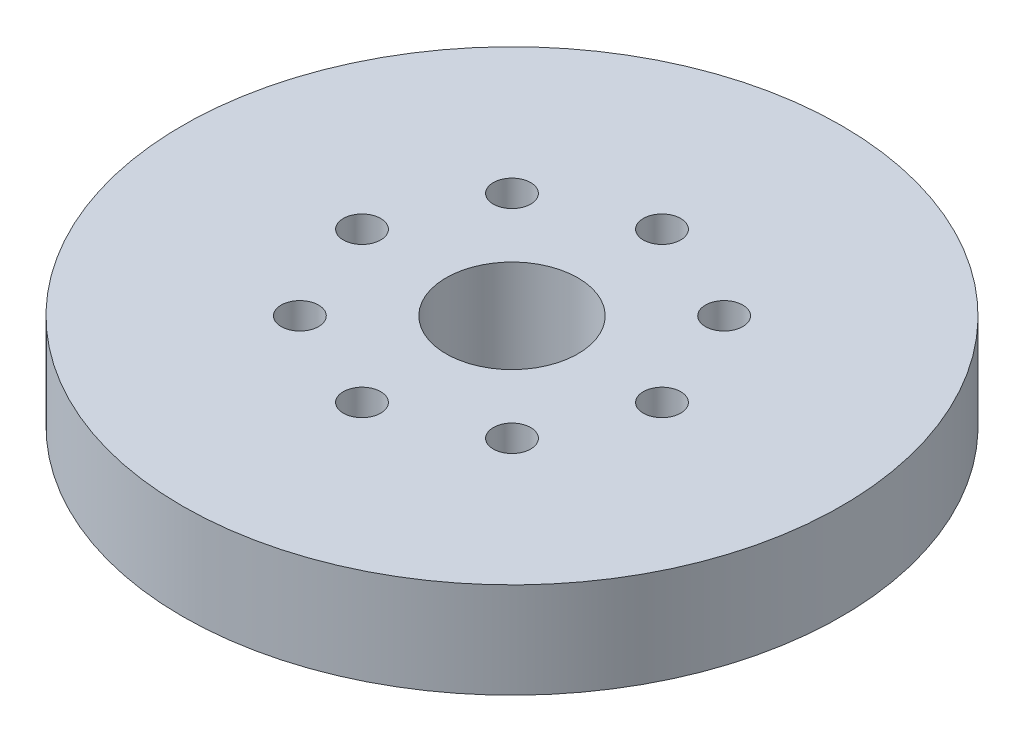
SolidWorks part; units mm, degrees
ref_plane "Front Plane" through (0, 0, 0) normal (0, 0, 1) x (1, 0, 0)
ref_plane "Top Plane" through (0, 0, 0) normal (0, 1, 0) x (1, 0, 0)
ref_plane "Right Plane" through (0, 0, 0) normal (1, 0, 0) x (0, 0, -1)
sketch "Sketch1" plane through (0, 0, 0) normal (0, 1, 0) x (1, 0, 0)
  circle A0 centre (0, 0) radius 100
  dimension "FLANGE_OD" = 200
extrude "Boss-Extrude1" add sketch "Sketch1" along normal blind 29
sketch "Sketch2" plane through (0, 0, 0) normal (0, 1, 0) x (1, 0, 0)
  circle A0 centre (0, 0) radius 20
  dimension "BORE_D" = 40
extrude "Cut-Extrude1" cut sketch "Sketch2" along normal through all
sketch "Sketch3" plane through (0, 29, 0) normal (0, 1, 0) x (1, 0, 0)
  circle A0 centre (0, 0) radius 45.5146 construction
  circle A1 centre (-45.5146, 0) radius 5.6716
  dimension "BOLT_D" = 11.3431
  dimension "BOLT_PCD" = 91.0292
extrude "Cut-Extrude2" cut sketch "Sketch3" against normal blind 26.0182
pattern_circular "CirPattern1" count 8 over 360 about axis through (0, 0, 0) along (0, 1, 0) of "Cut-Extrude2"
